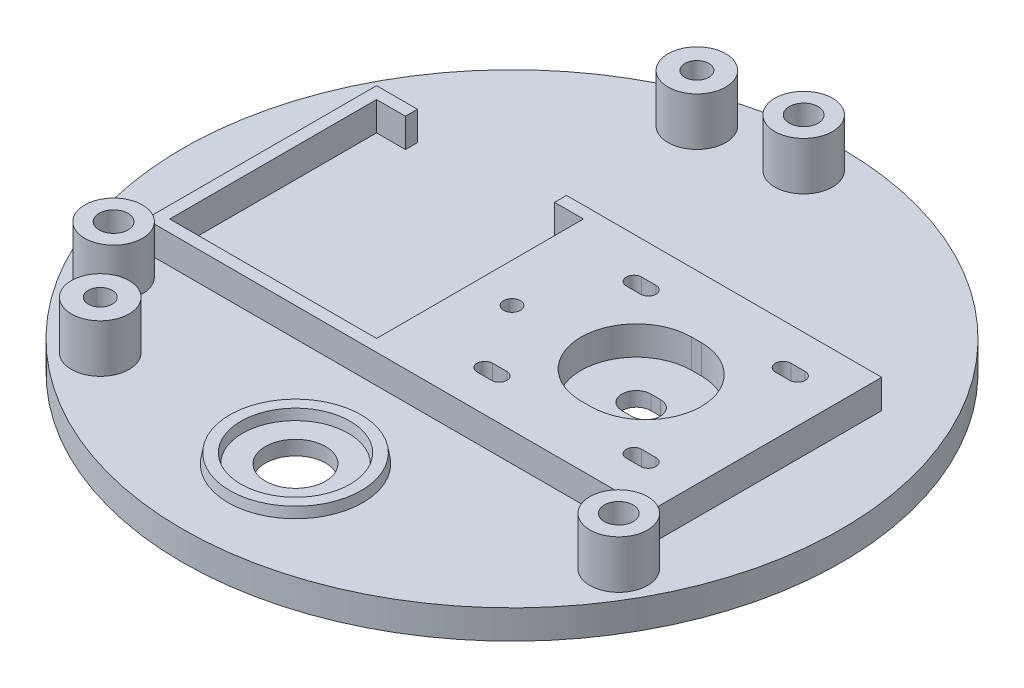
SolidWorks part; units mm, degrees
material "ABS"
ref_plane "Front Plane" through (0, 0, 0) normal (0, 0, 1) x (1, 0, 0)
ref_plane "Top Plane" through (0, 0, 0) normal (0, 1, 0) x (1, 0, 0)
ref_plane "Right Plane" through (0, 0, 0) normal (1, 0, 0) x (0, 0, -1)
sketch "Sketch1" plane through (0, 0, 0) normal (0, 0, 1) x (1, 0, 0)
  line L0 (0, 0) -> (68.5, 0)
  line L1 (68.5, 0) -> (68.5, -6)
  line L2 (68.5, -6) -> (66.5, -6)
  line L3 (66.5, -6) -> (66.5, -3)
  line L5 (53.5, -3) -> (53.5, -6)
  line L6 (53.5, -6) -> (50.5, -6)
  line L7 (50.5, -6) -> (50.5, -3)
  line L8 (50.5, -3) -> (6, -3)
  line L9 (6, -3) -> (6, -5)
  line L10 (6, -5) -> (0, -5)
  line L11 (0, -5) -> (0, 0)
  line L12 (62.3516, -3) -> (66.5, -3)
  line L13 (57.6484, -3) -> (53.5, -3)
  arc A0 (62.3516, -3) -> (57.6484, -3) centre (60, -6.6) ccw
  point P4 (67.5, -6)
  dimension "D2" = 4.3
  dimension "D1" = 60
  dimension "D3" = 6.5
  dimension "D4" = 3
  dimension "D5" = 6.5
  dimension "D6" = 3
  dimension "D7" = 2
  dimension "D8" = 50.5
  dimension "D9" = 0.6
  dimension "D10" = 5
  dimension "D11" = 6
revolve "Revolve1" add sketch "Sketch1" angle 360 about L11
sketch "Sketch2" plane through (0, 0, 0) normal (0, 1, 0) x (1, 0, 0)
  line L0 (-52.5, -30.3109) -> (0, 60.6218) construction
  line L1 (0, 60.6218) -> (52.5, -30.3109) construction
  line L2 (52.5, -30.3109) -> (-52.5, -30.3109) construction
  line L3 (0, 0) -> (0, 60.6218) construction
  line L4 (0, 0) -> (52.5, -30.3109) construction
  line L5 (0, 0) -> (-52.5, -30.3109) construction
  line L6 (0, 0) -> (0, -45) construction
  line L7 (-40.2731, -45.3109) -> (-40.2731, -30.3109) construction
  line L8 (-19.1038, 57.533) -> (-6.1134, 50.033) construction
  circle A0 centre (0, 60.6218) radius 6
  circle A1 centre (0, 60.6218) radius 3
  circle A2 centre (52.5, -30.3109) radius 6
  circle A3 centre (-52.5, -30.3109) radius 6
  circle A4 centre (-52.5, -30.3109) radius 3
  circle A5 centre (52.5, -30.3109) radius 3
  circle A6 centre (0, -45) radius 6.25 construction
  arc A7 (0, 60.6218) -> (-24.7136, -55.3555) centre (0, 0) ccw construction
  circle A8 centre (-40.2731, -45.3109) radius 6
  circle A9 centre (-19.1038, 57.533) radius 6
  circle A10 centre (-40.2731, -45.3109) radius 2.5
  circle A11 centre (-19.1038, 57.533) radius 2.5
  arc A12 (15.6635, -19.9954) -> (14.3368, 20.9671) centre (0, 0) ccw construction
  dimension "D2" = 12
  dimension "D3" = 6
  dimension "D5" = 12.5
  dimension "D6" = 12
  dimension "D8" = 5
  dimension "D9" = 25.4
  dimension "D1" = 105
  dimension "D4" = 45
  dimension "D7" = 15
extrude "Boss-Extrude1" add sketch "Sketch2" along normal blind 10
sketch "Sketch3" plane through (0, 0, 0) normal (0, 1, 0) x (1, 0, 0)
  circle A0 centre (0, -45) radius 6.25
  circle A1 centre (0, -45) radius 6.25 construction
extrude "Cut-Extrude1" cut sketch "Sketch3" against normal blind 10
sketch "Sketch4" plane through (0, 0, 0) normal (0, 1, 0) x (1, 0, 0)
  circle A0 centre (0, -45) radius 11
  circle A1 centre (0, -45) radius 14
  dimension "D1" = 22
  dimension "D2" = 28
extrude "Boss-Extrude2" add sketch "Sketch4" along normal blind 2 draft 10
sketch "Sketch5" plane through (0, 0, 0) normal (0, 1, 0) x (1, 0, 0)
  line L0 (51.3563, -22.5103) -> (51.3563, 25.4897)
  line L1 (51.3563, -22.5103) -> (-53.6437, -22.5103)
  line L2 (51.3563, 25.4897) -> (-53.6437, 25.4897) construction
  line L3 (-53.6437, -22.5103) -> (-53.6437, 25.4897)
  line L4 (-51.1437, 22.9897) -> (-45.1437, 22.9897)
  line L5 (-53.6437, 1.4897) -> (51.3563, 1.4897) construction
  line L6 (25.3563, 1.4897) -> (25.3563, 25.4897) construction
  line L7 (26.3563, 1.4897) -> (24.3563, 1.4897) construction
  line L8 (26.3563, -10.0103) -> (24.3563, -10.0103)
  line L9 (26.3563, 12.9897) -> (24.3563, 12.9897)
  line L10 (-45.1437, 22.9897) -> (-45.1437, 25.4897)
  line L11 (-51.1437, -20.0103) -> (-51.1437, 22.9897)
  line L12 (-51.1437, 22.9897) -> (-8.1437, 22.9897) construction
  line L13 (-8.1437, 22.9897) -> (-8.1437, -20.0103)
  line L14 (-8.1437, -20.0103) -> (-51.1437, -20.0103)
  line L15 (-45.1437, 25.4897) -> (-53.6437, 25.4897)
  line L16 (-8.1437, 22.9897) -> (-14.1437, 22.9897)
  line L17 (-14.1437, 22.9897) -> (-14.1437, 25.4897)
  line L18 (-14.1437, 25.4897) -> (51.3563, 25.4897)
  arc A1 (26.3563, -10.0103) -> (26.3563, 12.9897) centre (26.3563, 1.4897) ccw
  arc A2 (24.3563, 12.9897) -> (24.3563, -10.0103) centre (24.3563, 1.4897) ccw
  arc A3 (15.6635, -19.9954) -> (14.3368, 20.9671) centre (0, 0) ccw construction
  point P10 (25.3563, 1.4897)
  point P18 (-8.1437, 1.4897)
  point P23 (0, 0)
  dimension "D3" = 23
  dimension "D1" = 48
  dimension "D2" = 105
  dimension "D4" = 2
  dimension "D5" = 26
  dimension "D6" = 2.5
  dimension "D7" = 43
  dimension "D8" = 43
  dimension "D9" = 6
  dimension "D10" = 6
extrude "Boss-Extrude3" add sketch "Sketch5" along normal blind 6
sketch "Sketch6" plane through (0, 6, 0) normal (0, 1, 0) x (1, 0, 0)
  line L0 (40.8563, -14.0103) -> (40.8563, 16.9897) construction
  line L1 (40.8563, -14.0103) -> (9.8563, -14.0103) construction
  line L2 (40.8563, 16.9897) -> (9.8563, 16.9897) construction
  line L3 (9.8563, -14.0103) -> (9.8563, 16.9897) construction
  line L4 (40.8563, -14.0103) -> (9.8563, 16.9897) construction
  line L5 (40.8563, 16.9897) -> (9.8563, -14.0103) construction
  line L6 (25.3563, 1.4897) -> (25.3563, 25.4897) construction
  line L7 (11.3563, -14.0103) -> (8.3563, -14.0103) construction
  line L8 (11.3563, -15.6103) -> (8.3563, -15.6103)
  line L9 (11.3563, -12.4103) -> (8.3563, -12.4103)
  line L10 (42.3563, -14.0103) -> (39.3563, -14.0103) construction
  line L11 (42.3563, -15.6103) -> (39.3563, -15.6103)
  line L12 (42.3563, -12.4103) -> (39.3563, -12.4103)
  line L13 (42.3563, 16.9897) -> (39.3563, 16.9897) construction
  line L14 (42.3563, 15.3897) -> (39.3563, 15.3897)
  line L15 (42.3563, 18.5897) -> (39.3563, 18.5897)
  line L16 (11.3563, 16.9897) -> (8.3563, 16.9897) construction
  line L17 (11.3563, 15.3897) -> (8.3563, 15.3897)
  line L18 (11.3563, 18.5897) -> (8.3563, 18.5897)
  arc A0 (11.3563, -15.6103) -> (11.3563, -12.4103) centre (11.3563, -14.0103) ccw
  arc A1 (8.3563, -12.4103) -> (8.3563, -15.6103) centre (8.3563, -14.0103) ccw
  arc A2 (42.3563, -15.6103) -> (42.3563, -12.4103) centre (42.3563, -14.0103) ccw
  arc A3 (39.3563, -12.4103) -> (39.3563, -15.6103) centre (39.3563, -14.0103) ccw
  arc A4 (42.3563, 15.3897) -> (42.3563, 18.5897) centre (42.3563, 16.9897) ccw
  arc A5 (39.3563, 18.5897) -> (39.3563, 15.3897) centre (39.3563, 16.9897) ccw
  arc A6 (11.3563, 15.3897) -> (11.3563, 18.5897) centre (11.3563, 16.9897) ccw
  arc A7 (8.3563, 18.5897) -> (8.3563, 15.3897) centre (8.3563, 16.9897) ccw
  point P1 (25.3563, 1.4897)
  point P2 (25.3563, 16.9897)
  point P11 (9.8563, -14.0103)
  point P21 (40.8563, -14.0103)
  point P28 (40.8563, 16.9897)
  point P35 (9.8563, 16.9897)
  dimension "D2" = 1.6
  dimension "D1" = 31
  dimension "D3" = 3
  dimension "D4" = 2
  dimension "D5" = 2
extrude "Cut-Extrude2" cut sketch "Sketch6" against normal through all
sketch "Sketch7" plane through (0, 0, 0) normal (0, 1, 0) x (1, 0, 0)
  line L0 (26.3563, 1.4897) -> (24.3563, 1.4897) construction
  line L1 (26.3563, -1.5103) -> (24.3563, -1.5103)
  line L2 (26.3563, 4.4897) -> (24.3563, 4.4897)
  arc A0 (26.3563, -1.5103) -> (26.3563, 4.4897) centre (26.3563, 1.4897) ccw
  arc A1 (24.3563, 4.4897) -> (24.3563, -1.5103) centre (24.3563, 1.4897) ccw
  point P2 (25.3563, 1.4897)
  dimension "D1" = 3
extrude "Cut-Extrude3" cut sketch "Sketch7" against normal through all
sketch "Sketch8" plane through (0, 6, 0) normal (0, 1, 0) x (1, 0, 0)
  circle A0 centre (0, 0) radius 1.75
  dimension "D1" = 3.5
extrude "Cut-Extrude4" cut sketch "Sketch8" against normal through all
